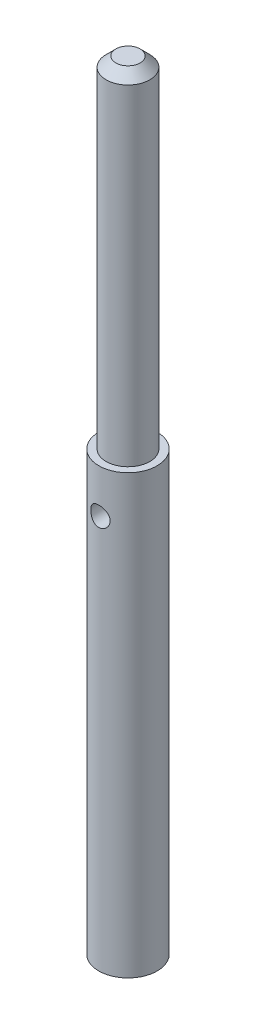
SolidWorks part; units mm, degrees
ref_plane "Przednia" through (0, 0, 0) normal (0, 0, 1) x (1, 0, 0)
ref_plane "Górna" through (0, 0, 0) normal (0, 1, 0) x (1, 0, 0)
ref_plane "Prawa" through (0, 0, 0) normal (1, 0, 0) x (0, 0, -1)
sketch "Szkic1" plane through (0, 0, 0) normal (0, 1, 0) x (1, 0, 0)
  circle A0 centre (0, 0) radius 3
  dimension "D1" = 6
extrude "Dodanie-wyciągnięcie1" add sketch "Szkic1" along normal blind 45
sketch "Szkic2" plane through (0, 0, 0) normal (0, 0, 1) x (1, 0, 0)
  line L0 (3, 45) -> (-3, 45) construction
  circle A0 centre (0, 40.5) radius 1
  dimension "D2" = 2
  dimension "D1" = 4.5
extrude "Wytnij-wyciągnięcie1" cut sketch "Szkic2" against normal mid plane 40
sketch "Szkic9" plane through (0, 45, 0) normal (0, 1, 0) x (1, 0, 0)
  circle A0 centre (0, 0) radius 2.25
  dimension "D1" = 4.5
extrude "Dodanie-wyciągnięcie2" add sketch "Szkic9" along normal blind 24
sketch "Szkic13" plane through (0, 69, 0) normal (0, 1, 0) x (1, 0, 0)
  circle A0 centre (0, 0) radius 2.25
  dimension "D1" = 4.5
extrude "Dodanie-wyciągnięcie9" add sketch "Szkic13" along normal blind 11
chamfer "Sfazowanie8" distance 1 angle 45 1 edges at (0, 80, 2.25)
